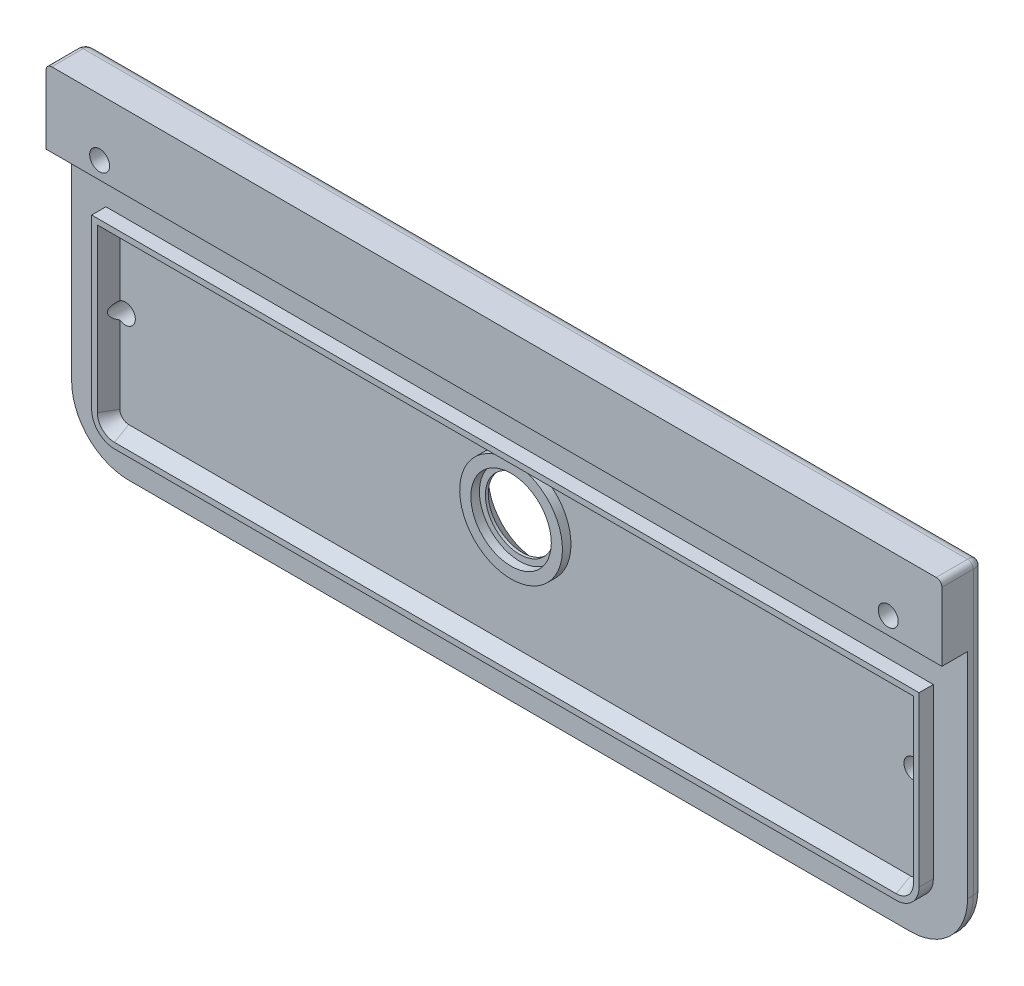
SolidWorks part; units mm, degrees
ref_plane "Front Plane" through (0, 0, 0) normal (0, 0, 1) x (1, 0, 0)
ref_plane "Top Plane" through (0, 0, 0) normal (0, 1, 0) x (1, 0, 0)
ref_plane "Right Plane" through (0, 0, 0) normal (1, 0, 0) x (0, 0, -1)
sketch "Sketch1" plane through (0, 0, 0) normal (0, 0, 1) x (1, 0, 0)
  line L0 (0, 35.5) -> (147, 35.5)
  line L1 (5, 0) -> (142, 0)
  line L2 (0, 5) -> (0, 55.5)
  line L3 (0, 55.5) -> (147, 55.5)
  line L4 (147, 5) -> (147, 55.5)
  line L5 (0, 42.5) -> (147, 42.5)
  line L6 (73.5, 0) -> (73.5, 55.5) construction
  line L7 (63.5, 0) -> (63.5, 35.5) construction
  arc A0 (142, 0) -> (147, 5) centre (142, 5) ccw
  arc A1 (5, 0) -> (0, 5) centre (5, 5) cw
  circle A2 centre (4.4, 17.75) radius 1.75
  circle A3 centre (142.6, 17.75) radius 1.75
  point P11 (147, 0)
  point P14 (0, 0)
  point P24 (63.5, 17.75)
  dimension "D5" = 5
  dimension "D6" = 3.5
  dimension "D1" = 147
  dimension "D2" = 55.5
  dimension "D3" = 35.5
  dimension "D4" = 42.5
  dimension "D7" = 138.2
  dimension "D8" = 10
sketch "Sketch2" plane through (0, 0, 0) normal (0, 0, 1) x (1, 0, 0)
  line L36 (0, 55.5) -> (147, 55.5) construction
  line L37 (-4, 55.5) -> (151, 55.5)
  line L38 (73.5, -5) -> (73.5, 55.5) construction
  line L40 (-5, 60.5) -> (-5, 5)
  line L41 (5, -5) -> (142, -5)
  line L42 (152, 5) -> (152, 60.5)
  line L43 (152, 60.5) -> (-5, 60.5)
  line L44 (-5, 54.5) -> (-5, 5)
  line L45 (5, -5) -> (142, -5)
  line L46 (152, 5) -> (152, 54.5)
  arc A0 (151, 55.5) -> (152, 54.5) centre (151, 54.5) cw
  arc A1 (-4, 55.5) -> (-5, 54.5) centre (-4, 54.5) ccw
  arc A25 (-5, 5) -> (5, -5) centre (5, 5) ccw
  arc A26 (142, -5) -> (152, 5) centre (142, 5) ccw
  arc A27 (-5, 5) -> (5, -5) centre (5, 5) ccw
  arc A28 (142, -5) -> (152, 5) centre (142, 5) ccw
  circle A29 centre (142.6, 20) radius 1.75
  circle A30 centre (4.4, 20) radius 1.75
  circle A31 centre (4.4, 45.5) radius 1.75
  circle A32 centre (142.6, 45.5) radius 1.75
  dimension "D3" = 1
  dimension "D2" = 10
  dimension "D4" = 20
  dimension "D1" = 5
extrude "Boss-Base" add sketch "Sketch2" along normal blind 3
sketch "Sketch3" plane through (0, 0, 3) normal (0, 0, 1) x (1, 0, 0)
  line L21 (5, 1) -> (142, 1)
  line L22 (0, 33.5) -> (147, 33.5)
  line L23 (2, 33.5) -> (145, 33.5)
  line L24 (2, 53.5) -> (2, 5)
  line L25 (145, 53.5) -> (2, 53.5)
  line L26 (145, 5) -> (145, 53.5)
  line L27 (5, 2) -> (142, 2)
  line L28 (2, 33.5) -> (2, 5)
  line L30 (145, 5) -> (145, 33.5)
  line L31 (5, 2) -> (142, 2)
  line L32 (146, 5) -> (146, 34.5)
  line L33 (1, 34.5) -> (146, 34.5)
  line L34 (1, 34.5) -> (1, 5)
  arc A10 (1, 5) -> (5, 1) centre (5, 5) ccw
  arc A11 (142, 1) -> (146, 5) centre (142, 5) ccw
  arc A12 (2, 5) -> (5, 2) centre (5, 5) ccw
  arc A13 (142, 2) -> (145, 5) centre (142, 5) ccw
  arc A14 (2, 5) -> (5, 2) centre (5, 5) ccw
  arc A15 (142, 2) -> (145, 5) centre (142, 5) ccw
  dimension "D1" = 2
  dimension "D2" = 2
  dimension "D3" = 1
extrude "Boss-Fit" add sketch "Sketch3" along normal blind 2.5
chamfer "Chamfer1" distance 2.5 angle 30 6 edges at (145, 19.25, 3) (144.1213, 2.8787, 3) (73.5, 2, 3) (2.8787, 2.8787, 3) (2, 19.25, 3) (73.5, 33.5, 3) first distance on face at (145, 19.25, 4.25) first distance on face at (143.8107, 3.1893, 4.25) first distance on face at (73.5, 2, 4.25) first distance on face at (3.1893, 3.1893, 4.25) first distance on face at (2, 19.25, 4.25) first distance on face at (73.5, 33.5, 4.25)
sketch "Sketch4" plane through (0, 0, 3) normal (0, 0, 1) x (1, 0, 0)
  line L3 (-5, 54.5) -> (-5, 5) construction
  line L5 (152, 5) -> (152, 54.5) construction
  line L6 (-4, 55.5) -> (151, 55.5) construction
  line L7 (-5, 54.5) -> (-5, 42.5)
  line L9 (152, 42.5) -> (152, 54.5)
  line L10 (-4, 55.5) -> (151, 55.5)
  line L11 (-5, 42.5) -> (152, 42.5)
  arc A0 (-4, 55.5) -> (-5, 54.5) centre (-4, 54.5) ccw construction
  arc A3 (152, 54.5) -> (151, 55.5) centre (151, 54.5) ccw construction
  arc A4 (-4, 55.5) -> (-5, 54.5) centre (-4, 54.5) ccw
  arc A7 (152, 54.5) -> (151, 55.5) centre (151, 54.5) ccw
  circle A8 centre (142.6, 45.5) radius 1.75 construction
  circle A9 centre (4.4, 45.5) radius 1.75 construction
  circle A10 centre (142.6, 45.5) radius 1.75
  circle A11 centre (4.4, 45.5) radius 1.75
  dimension "D1" = 13
extrude "Boss-TopFit" add sketch "Sketch4" along normal blind 4.5
fillet "Fillet1" radius 2 8 edges at (73.5, 55.5, 0) (-4.7071, 55.2071, 0) (-5, 29.75, 0) (-2.0711, -2.0711, 0) (73.5, -5, 0) (149.0711, -2.0711, 0) (152, 29.75, 0) (151.7071, 55.2071, 0)
sketch "Sketch10" plane through (0, 0, 0) normal (0, 0, -1) x (-1, 0, 0)
  line L0 (-140.7988, 14) -> (-145, 8)
  line L7 (-145, 8) -> (-142.25, 8)
  line L8 (-142.25, 8) -> (-138.0488, 14)
  line L9 (-138.0488, 14) -> (-140.7988, 14)
  line L10 (-136.0488, 14) -> (-144.4512, 2)
  line L11 (-144.4512, 2) -> (-141.7012, 2)
  line L12 (-141.7012, 2) -> (-133.2988, 14)
  line L13 (-133.2988, 14) -> (-136.0488, 14)
  line L14 (-135.5, 8) -> (-139.7012, 2)
  line L15 (-139.7012, 2) -> (-136.9512, 2)
  line L16 (-136.9512, 2) -> (-132.75, 8)
  line L17 (-132.75, 8) -> (-135.5, 8)
  line L18 (-150, 53.5) -> (-150, 5) construction
  line L19 (-142, -3) -> (-5, -3) construction
  dimension "D1" = 12
  dimension "D2" = 6
  dimension "D3" = 2.75
  dimension "D4" = 2
  dimension "D5" = 2
  dimension "D6" = 55
  dimension "D7" = 5
  dimension "D8" = 5
extrude "Cut-Voron" cut sketch "Sketch10" against normal blind 0.6
sketch "Sketch11" plane through (0, 0, 3) normal (0, 0, 1) x (1, 0, 0)
  line L0 (73.5, 3.4434) -> (73.5, 66.2444) construction
  line L1 (5, 3.4434) -> (142, 3.4434) construction
  circle A0 centre (73.5, 24) radius 9
  dimension "D2" = 18
  dimension "D1" = 24
extrude "Boss-Bearing" add sketch "Sketch11" along normal blind 1.5
sketch "Sketch8" plane through (0, 0, 4.5) normal (0, 0, 1) x (1, 0, 0)
  line L0 (73.5, 3.4434) -> (73.5, 66.4675) construction
  line L1 (5, 3.4434) -> (142, 3.4434) construction
  circle A0 centre (73.5, 24) radius 7.05
  dimension "D2" = 14.1
  dimension "D1" = 24
extrude "Cut-Bearing" cut sketch "Sketch8" against normal offset from surface (1.5 mm away) 3 up to face at (138.875, 8, 0)
sketch "Sketch9" plane through (0, 0, 3) normal (0, 0, 1) x (1, 0, 0)
  circle A0 centre (73.5, 24) radius 6
  dimension "D1" = 12
extrude "Cut-Bearing2" cut sketch "Sketch9" against normal through all
chamfer "Chamfer2" distance 2.5 angle 45 1 edges at (79.5, 24, 0)
equation "\"width\"=147"
equation "\"D1@Sketch1\"=\"width\""
equation "\"height\"=42.5"
equation "\"height_outside\"=55.5"
equation "\"D2@Sketch1\"=\"height_outside\""
equation "\"height_inside\"=35.5"
equation "\"D3@Sketch1\"=\"height_inside\""
equation "\"D4@Sketch1\"=\"height\""
